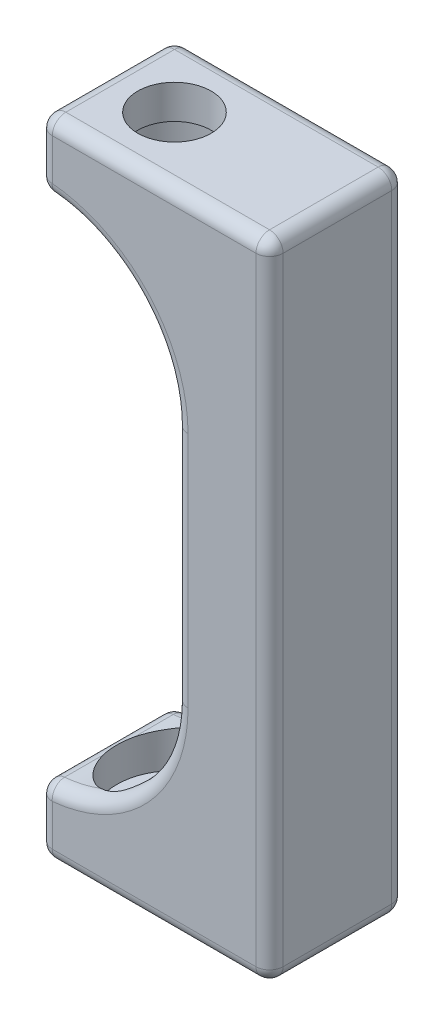
SolidWorks part; units mm, degrees
ref_plane "Front Plane" through (0, 0, 0) normal (0, 0, 1) x (1, 0, 0)
ref_plane "Top Plane" through (0, 0, 0) normal (0, 1, 0) x (1, 0, 0)
ref_plane "Right Plane" through (0, 0, 0) normal (1, 0, 0) x (0, 0, -1)
sketch "Sketch1" plane through (0, 0, 0) normal (0, 0, 1) x (1, 0, 0)
  line L0 (3.5, 0) -> (-32.6297, 0) construction
  line L1 (-3.5, -23.75) -> (3.5, -23.75)
  line L2 (-3.5, -23.75) -> (-3.5, 23.75)
  line L3 (-3.5, 23.75) -> (3.5, 23.75)
  line L4 (3.5, -23.75) -> (3.5, 23.75)
  line L5 (-3.5, -23.75) -> (3.5, 23.75) construction
  line L6 (-3.5, 23.75) -> (3.5, -23.75) construction
  line L7 (-3.5, 18.75) -> (-13.5, 18.75)
  line L8 (-3.5, -23.75) -> (-13.5, -23.75)
  line L9 (-3.5, -23.75) -> (-3.5, -18.75)
  line L10 (-3.5, -18.75) -> (-13.5, -18.75)
  line L11 (-13.5, -23.75) -> (-13.5, -18.75)
  line L12 (-13.5, 23.75) -> (-13.5, 18.75)
  line L13 (-3.5, 23.75) -> (-13.5, 23.75)
  point P0 (0, 0)
  dimension "D1" = 47.5
  dimension "D2" = 7
  dimension "D3" = 10
  dimension "D4" = 5
extrude "Boss-Extrude1" add sketch "Sketch1" along normal blind 10 contours L2 L13 L12 L7 | L1 L4 L3 L2 | L11 L8 L2 L10 region at (0, 0, 0) region at (-8.5, -21.25, 0) region at (-8.5, 21.25, 0)
sketch "Sketch2" plane through (0, -18.75, 0) normal (0, 1, 0) x (1, 0, 0)
  line L0 (-3.5, 0) -> (-3.5, -10)
  line L1 (3.5, -10) -> (-13.5, -10) construction
  line L2 (-8.5, 0) -> (-8.5, -10) construction
  line L3 (-3.5, -10) -> (-13.5, -10)
  line L4 (-3.5, -10) -> (-3.5, 0)
  line L5 (-3.5, 0) -> (-13.5, 0)
  line L6 (-13.5, -10) -> (-13.5, 0)
  line L7 (-3.5, -5) -> (-13.5, -5) construction
  circle A0 centre (-8.5, -5) radius 4.25
  circle A1 centre (-8.5, -5) radius 2.7
  dimension "D1" = 8.5
  dimension "D2" = 5.4
extrude "Cut-Extrude1" cut sketch "Sketch2" against normal through all both and the other way through all contours A1 region at (-8.5, -18.75, 5)
extrude "Cut-Extrude2" cut sketch "Sketch2<3>" against normal blind 2.5 and the other way blind 40 contours A0 A1 region at (-12.6298, -18.75, 5)
sketch "Sketch2<3>" plane through (0, -18.75, 0) normal (0, 1, 0) x (1, 0, 0) same geometry as "Sketch2"
fillet "Fillet1" radius 10 2 edges at (-3.5, -18.75, 5) (-3.5, 18.75, 5)
fillet "Fillet2" radius 1 22 edges at (-13.5, -18.75, 5) (-13.5, -23.75, 5) (-13.5, 23.75, 5) (-13.5, 18.75, 5) (3.5, -23.75, 5) (3.5, 23.75, 5) (-6.4289, -15.8211, 0) (-13.5, -21.25, 0) (-5, -23.75, 0) (3.5, 0, 0) (-5, 23.75, 0) (-13.5, 21.25, 0) (-6.4289, 15.8211, 0) (-3.5, 0, 0) (-5, 23.75, 10) (3.5, 0, 10) (-5, -23.75, 10) (-13.5, -21.25, 10) (-6.4289, -15.8211, 10) (-3.5, 0, 10) (-6.4289, 15.8211, 10) (-13.5, 21.25, 10)
